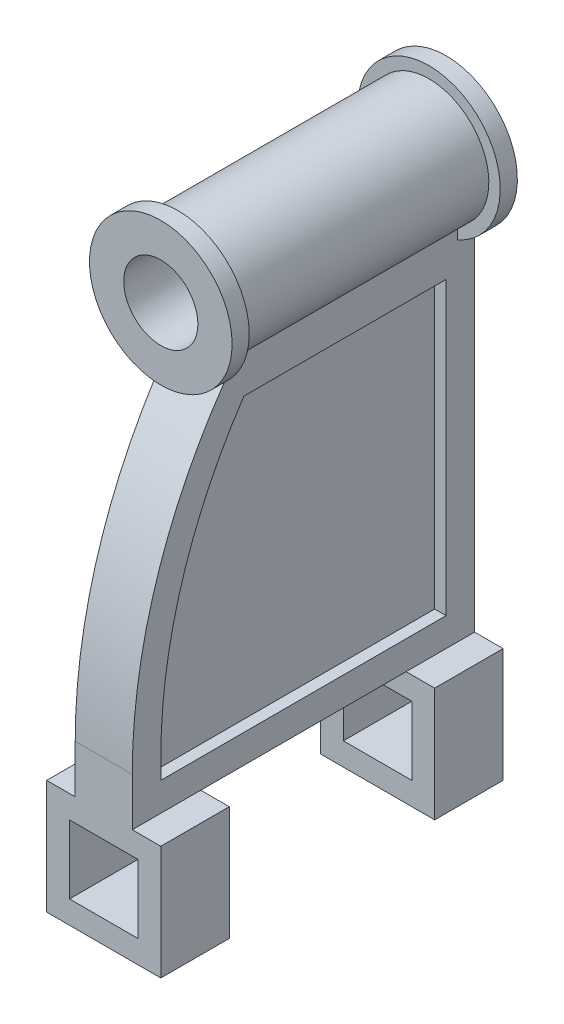
SolidWorks part; units mm, degrees
material "1060 Alloy"
ref_plane "Front Plane" through (0, 0, 0) normal (0, 0, 1) x (1, 0, 0)
ref_plane "Top Plane" through (0, 0, 0) normal (0, 1, 0) x (1, 0, 0)
ref_plane "Right Plane" through (0, 0, 0) normal (1, 0, 0) x (0, 0, -1)
ref_plane "Plane1" through (0, 0, 5) normal (0, 0, 1) x (1, 0, 0)
sketch "Sketch1" plane through (0, 0, 0) normal (0, 0, 1) x (1, 0, 0)
  line L0 (0, 0) -> (0, 40) construction
  circle A0 centre (0, 40) radius 12.5
  dimension "D1" = 25
  dimension "D2" = 40
extrude "BE1" add sketch "Sketch1" along normal mid plane 50
sketch "Sketch2" plane through (0, 0, 25) normal (0, 0, 1) x (1, 0, 0)
  circle A2 centre (0, 40) radius 6.5
  circle A3 centre (0, 40) radius 6.5
  dimension "D1" = 6
extrude "CE1" cut sketch "Sketch2" against normal through all
sketch "Sketch3" plane through (0, 0, 0) normal (1, 0, 0) x (0, 0, -1)
  line L1 (-35, -32.5) -> (25, -32.5)
  line L3 (-15, 32.5) -> (25, 32.5)
  line L4 (25, -32.5) -> (25, 32.5)
  line L5 (-35, -32.5) -> (-35, -24.0685)
  line L6 (-15.8258, 20.5735) -> (25, -32.5) construction
  arc A1 (-35, -24.0685) -> (-15, 32.5) centre (55, -24.0685) cw
  point P0 (0, 0)
  dimension "D3" = 40
  dimension "D4" = 90
  dimension "D1" = 65
  dimension "D2" = 60
  dimension "D5" = 32.5
  dimension "D6" = 25
extrude "BE2" add sketch "Sketch3" along normal mid plane 10
sketch "Sketch4" plane through (0, 0, 35) normal (0, 0, 1) x (1, 0, 0)
  line L0 (0, -42.5) -> (0, -32.5) construction
  line L1 (5, -32.5) -> (-5, -32.5) construction
  line L8 (-10, -52.5) -> (10, -52.5)
  line L9 (-10, -52.5) -> (-10, -32.5)
  line L10 (-10, -32.5) -> (10, -32.5)
  line L11 (10, -52.5) -> (10, -32.5)
  line L12 (-10, -52.5) -> (10, -32.5) construction
  line L13 (-10, -32.5) -> (10, -52.5) construction
  line L14 (6, -48.5) -> (-6, -48.5)
  line L15 (6, -48.5) -> (6, -36.5)
  line L16 (6, -36.5) -> (-6, -36.5)
  line L17 (-6, -48.5) -> (-6, -36.5)
  line L18 (6, -48.5) -> (-6, -36.5) construction
  line L19 (6, -36.5) -> (-6, -48.5) construction
  dimension "D1" = 20
  dimension "D3" = 20
  dimension "D2" = 10
  dimension "D4" = 12
extrude "BE3" add sketch "Sketch4" against normal blind 12
mirror "M1" about plane through (0, 0, 5) normal (0, 0, 1) of "BE3"
sketch "Sketch5" plane through (5, 0, 0) normal (1, 0, 0) x (0, 0, -1)
  line L0 (-23, -32.5) -> (13, -32.5) construction
  line L1 (-35, -24.0685) -> (-35, -32.5) construction
  circle A0 centre (-27, -24.5) radius 6
  circle A1 centre (-27, -24.5) radius 3
  dimension "D2" = 8
  dimension "D3" = 12
  dimension "D4" = 6
  dimension "D1" = 8
extrude "BE4" [suppressed] add sketch "Sketch5" along normal blind 6
sketch "Sketch6" plane through (5, 0, 0) normal (1, 0, 0) x (0, 0, -1)
  line L0 (-30, -24.0685) -> (-30, -27.5)
  line L7 (-30, -27.5) -> (-23, -27.5)
  line L9 (13, -27.5) -> (20, -27.5)
  line L24 (20, -27.5) -> (20, 23.5436)
  line L25 (20, 23.5436) -> (-15.4137, 23.5436)
  line L26 (-30, -24.0685) -> (-30, -27.5)
  line L29 (-23, -27.5) -> (13, -27.5)
  line L32 (20, -27.5) -> (20, 23.5436)
  line L33 (20, 23.5436) -> (-15.4137, 23.5436)
  line L37 (-30, -27.5) -> (20, -27.5)
  arc A3 (-15.4137, 23.5436) -> (-30, -24.0685) centre (55, -24.0685) ccw
  arc A4 (-15.4137, 23.5436) -> (-30, -24.0685) centre (55, -24.0685) ccw
  dimension "D1" = 5
extrude "CE2" cut sketch "Sketch6" against normal blind 2
mirror "M2" about plane through (0, 0, 0) normal (1, 0, 0) of "CE2", "BE4"
sketch "Sketch7" plane through (0, 0, -25) normal (0, 0, -1) x (-1, 0, 0)
  line L0 (-5, 28.5436) -> (-5, 30.7669)
  line L1 (5, 28.5436) -> (5, 30.7669)
  arc A0 (5, 30.7669) -> (-5, 30.7669) centre (0, 40) ccw
  arc A2 (5, 28.5436) -> (-5, 28.5436) centre (0, 40) ccw construction
  arc A3 (5, 28.5436) -> (-5, 28.5436) centre (0, 40) ccw
  dimension "D1" = 2
extrude "Cut-Extrude1" cut sketch "Sketch7" against normal offset from surface (44 mm away) 3 from offset 3 up to face at (6.5, 40, 25) offset against normal yes
sketch "Sketch8" plane through (0, 0, 25) normal (0, 0, 1) x (1, 0, 0)
  circle A0 centre (0, 40) radius 12.5
  circle A1 centre (0, 40) radius 10.5
  circle A2 centre (0, 40) radius 6.5 construction
  circle A3 centre (0, 40) radius 12.5 construction
  dimension "D1" = 2
extrude "Cut-Extrude2" cut sketch "Sketch8" against normal up to surface (13.7922 mm away) from offset 3 up to face at (0.6641, 2.716, 28.7151) offset against normal yes
